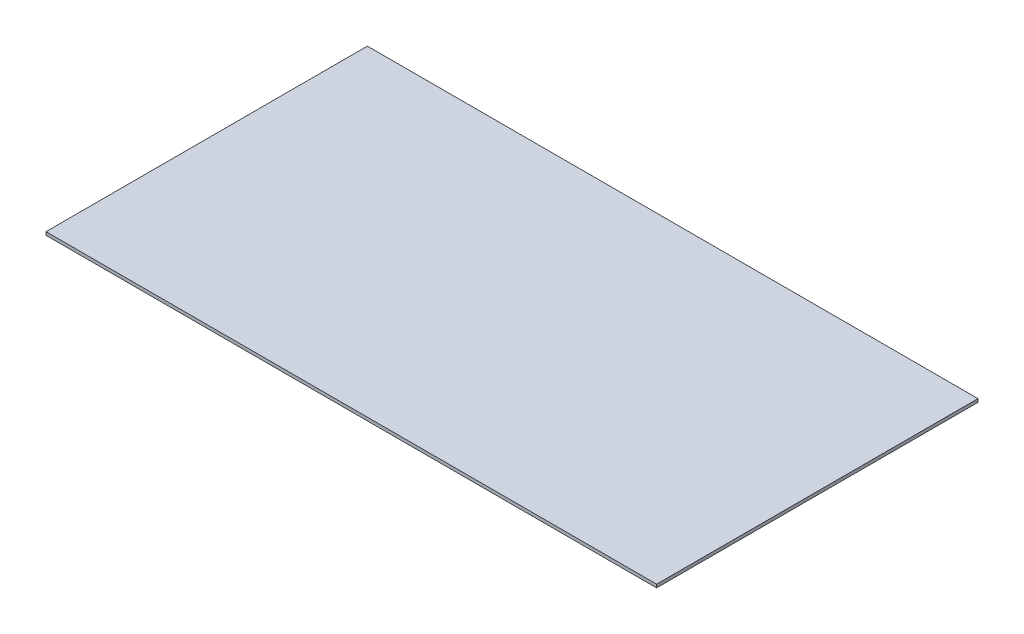
SolidWorks part; units mm, degrees
ref_plane "Front Plane" through (0, 0, 0) normal (0, 0, 1) x (1, 0, 0)
ref_plane "Top Plane" through (0, 0, 0) normal (0, 1, 0) x (1, 0, 0)
ref_plane "Right Plane" through (0, 0, 0) normal (1, 0, 0) x (0, 0, -1)
sketch "Sketch1" plane through (0, 0, 0) normal (0, 1, 0) x (1, 0, 0)
  line L3 (-190, 100) -> (190, 100)
  line L8 (-190, 100) -> (-190, -100)
  line L9 (-190, -100) -> (190, -100)
  line L10 (190, 100) -> (190, -100)
  line L11 (-190, 100) -> (190, -100) construction
  line L12 (-190, -100) -> (190, 100) construction
  point P0 (0, 0)
  dimension "D2" = 380
  dimension "D1" = 200
base flange "Base-Flange1" sketch "Sketch1" thickness 2 reverse thickness direction yes parameters "D1"=0.7366
sketch "Sketch8" plane through (0, 2, 0) normal (0, 1, 0) x (1, 0, 0)
  line L0 (-190, 0) -> (190, 0) construction
  line L1 (0, 100) -> (0, -100) construction
  line L2 (-175, 100) -> (-175, -100) construction
  line L3 (175, 100) -> (175, -100) construction
  line L4 (190, -100) -> (190, 100) construction
  line L5 (-190, 100) -> (-190, -100) construction
  line L6 (-175, 45.7976) -> (-175, -100) construction
  line L7 (190, 100) -> (-190, 100) construction
  line L8 (-190, -100) -> (190, -100) construction
  line L9 (0, 45.7976) -> (0, -100) construction
  line L10 (175, 45.7976) -> (175, -100) construction
  point P2 (190, 0)
  point P5 (-190, 0)
  point P15 (0, 0)
  point P16 (-175, 100)
  point P20 (-175, -100)
  point P23 (0, 100)
  point P25 (175, 100)
  point P27 (175, -100)
  point P28 (175, -100)
  dimension "D1" = 175
  dimension "D2" = 175
sketch "Bend-Lines1" [suppressed] plane through (0, 0, 0) normal (0, 1, 0) x (1, 0, 0)
sketch "Bounding-Box1" [suppressed] plane through (0, 0, 0) normal (0, 1, 0) x (1, 0, 0)
sheet metal parameters "Sheet-Metal1" thickness 2 parameters "D1"=0.7366
flat pattern "Flat-Pattern1" [suppressed]
sketch "Bend-Lines2" plane through (0, 0, 0) normal (0, 1, 0) x (1, 0, 0)
sketch3d "Bounding-Box2" [suppressed]
  line L0 (-190, -100, 0) -> (190, -100, 0) construction
  line L1 (-190, 100, 0) -> (190, 100, 0) construction
  line L2 (-190, -100, 0) -> (-190, 100, 0) construction
  line L3 (190, -100, 0) -> (190, 100, 0) construction
sketch "Sketch8-1" [suppressed] plane through (0, 2, 0) normal (0, 1, 0) x (1, 0, 0)
  line L0 (-250, 0) -> (250, 0) construction
  line L1 (0, 45.7976) -> (0, -40.2463) construction
  line L2 (-185, 45.7976) -> (-185, -40.2463) construction
  line L3 (185, 45.7976) -> (185, -40.2463) construction
